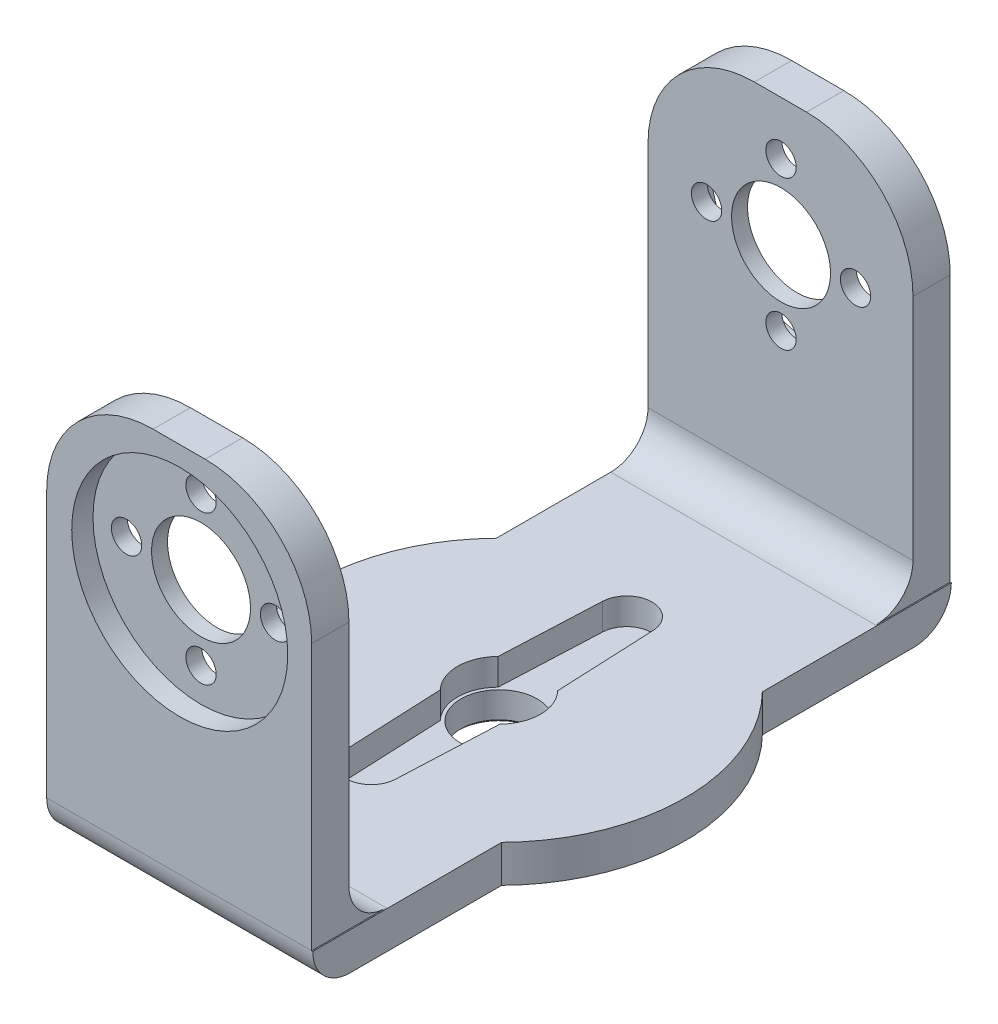
SolidWorks part; units mm, degrees
ref_plane "Alzado" through (0, 0, 0) normal (0, 0, 1) x (1, 0, 0)
ref_plane "Planta" through (0, 0, 0) normal (0, 1, 0) x (1, 0, 0)
ref_plane "Vista lateral" through (0, 0, 0) normal (1, 0, 0) x (0, 0, -1)
ref_plane "Plano1" through (0, 0, 30) normal (0, 0, 1) x (1, 0, 0)
sketch "Croquis1" plane through (0, 0, 0) normal (0, 1, 0) x (1, 0, 0)
  line L0 (1.9972, 12.1065) -> (2.53, 2.1187) construction
  line L1 (-1.9972, 12.1065) -> (-2.53, 2.1187) construction
  line L2 (-1.9972, -12.1065) -> (-2.53, -2.1187) construction
  line L3 (1.9972, -12.1065) -> (2.53, -2.1187) construction
  line L4 (1.9972, 12.1065) -> (2.53, 2.1187)
  line L5 (-1.9972, 12.1065) -> (-2.53, 2.1187)
  line L6 (-1.9972, -12.1065) -> (-2.53, -2.1187)
  line L7 (1.9972, -12.1065) -> (2.53, -2.1187)
  circle A0 centre (0, 0) radius 17.5
  circle A1 centre (0, 0) radius 1.65
  arc A2 (2.53, -2.1187) -> (2.53, 2.1187) centre (0, 0) ccw construction
  arc A3 (1.9972, 12.1065) -> (-1.9972, 12.1065) centre (0, 12) ccw construction
  arc A4 (-2.53, 2.1187) -> (-2.53, -2.1187) centre (0, 0) ccw construction
  arc A5 (-1.9972, -12.1065) -> (1.9972, -12.1065) centre (0, -12) ccw construction
  arc A6 (2.53, -2.1187) -> (2.53, 2.1187) centre (0, 0) ccw
  arc A7 (1.9972, 12.1065) -> (-1.9972, 12.1065) centre (0, 12) ccw
  arc A8 (-2.53, 2.1187) -> (-2.53, -2.1187) centre (0, 0) ccw
  arc A9 (-1.9972, -12.1065) -> (1.9972, -12.1065) centre (0, -12) ccw
  dimension "D1" = 35
  dimension "D2" = 3.3
extrude "Saliente-Extruir1" add sketch "Croquis1" along normal blind 3.5 contours A0 A1 | L6 A9 L7 A6 L4 A7 L5 A8 A1 region at (1.9763, 0, -7.0973) region at (-17.005, 0, 0)
sketch "Croquis2" plane through (0, 3.5, 0) normal (0, 1, 0) x (1, 0, 0)
  line L0 (-1.9972, -12.1065) -> (-2.53, -2.1187) construction
  line L1 (1.9972, -12.1065) -> (2.53, -2.1187) construction
  line L2 (1.9972, 12.1065) -> (2.53, 2.1187) construction
  line L3 (-1.9972, 12.1065) -> (-2.53, 2.1187) construction
  line L4 (-1.9972, -12.1065) -> (-2.53, -2.1187)
  line L5 (1.9972, -12.1065) -> (2.53, -2.1187)
  line L6 (1.9972, 12.1065) -> (2.53, 2.1187)
  line L7 (-1.9972, 12.1065) -> (-2.53, 2.1187)
  arc A1 (-2.53, 2.1187) -> (-2.53, -2.1187) centre (0, 0) ccw construction
  arc A2 (-1.9972, -12.1065) -> (1.9972, -12.1065) centre (0, -12) ccw construction
  arc A3 (2.53, -2.1187) -> (2.53, 2.1187) centre (0, 0) ccw construction
  arc A4 (1.9972, 12.1065) -> (-1.9972, 12.1065) centre (0, 12) ccw construction
  arc A5 (-2.53, 2.1187) -> (-2.53, -2.1187) centre (0, 0) ccw
  arc A6 (-1.9972, -12.1065) -> (1.9972, -12.1065) centre (0, -12) ccw
  arc A7 (2.53, -2.1187) -> (2.53, 2.1187) centre (0, 0) ccw
  arc A8 (1.9972, 12.1065) -> (-1.9972, 12.1065) centre (0, 12) ccw
extrude "Cortar-Extruir1" cut sketch "Croquis2" against normal blind 2.5
sketch "Croquis4" plane through (0, 1, 0) normal (0, 1, 0) x (1, 0, 0)
  circle A1 centre (0, 0) radius 3.3 construction
  circle A2 centre (0, 0) radius 3.3 construction
  circle A3 centre (0, 0) radius 3.6
  dimension "D1" = 0.3
extrude "Cortar-Extruir2" cut sketch "Croquis4" against normal through all both and the other way through all
sketch "Croquis8" plane through (0, 3.5, 0) normal (0, 1, 0) x (1, 0, 0)
  line L0 (3.9, 0) -> (3.9493, 0) construction
  line L1 (1.9972, -12.1065) -> (2.5051, -2.5854) construction
  line L2 (-2.5051, -2.5854) -> (-1.9972, -12.1065) construction
  line L3 (1.9972, -12.1065) -> (2.5051, -2.5854) construction
  line L4 (-2.5051, -2.5854) -> (-1.9972, -12.1065) construction
  line L5 (-2.7955, -2.7194) -> (-2.3743, -12.1065)
  line L6 (2.3743, -12.1065) -> (2.7955, -2.7194)
  line L7 (-3.9, 0) -> (-3.9493, 0) construction
  line L8 (2.3743, -12.1065) -> (1.9972, -12.1065) construction
  line L9 (-1.9972, -12.1065) -> (-2.3743, -12.1065) construction
  line L10 (2.4826, -3.0078) -> (2.7826, -3.0078) construction
  line L11 (-2.4826, -3.0078) -> (-2.7826, -3.0078) construction
  line L12 (2.7955, -2.7194) -> (-2.7955, -2.7194) construction
  line L13 (2.3743, 12.1065) -> (2.7955, 2.7194)
  line L14 (-2.7955, 2.7194) -> (-2.3743, 12.1065)
  line L15 (0, 0) -> (-3.6, 0) construction
  line L16 (0, 0) -> (3.6, 0) construction
  line L17 (-3.6, 0) -> (-3.9, 0) construction
  line L18 (3.6, 0) -> (3.9, 0) construction
  arc A0 (-2.7955, 2.7194) -> (-2.7955, -2.7194) centre (0, 0) ccw
  arc A1 (-1.9972, -12.1065) -> (1.9972, -12.1065) centre (0, -12) ccw construction
  arc A2 (-1.9972, -12.1065) -> (1.9972, -12.1065) centre (0, -12) ccw construction
  arc A3 (-2.3743, -12.1065) -> (2.3743, -12.1065) centre (0, -12) ccw
  arc A4 (-2.7955, -2.7194) -> (-2.4826, -3.0078) centre (0, 0) ccw construction
  arc A5 (2.7955, -2.7194) -> (2.7955, 2.7194) centre (0, 0) ccw
  arc A6 (-2.4826, -3.0078) -> (2.4826, -3.0078) centre (0, 0) ccw construction
  arc A7 (2.4826, -3.0078) -> (2.7955, -2.7194) centre (0, 0) ccw construction
  arc A8 (-2.3743, 12.1065) -> (2.3743, 12.1065) centre (0, 12) cw
  arc A9 (2.5051, -2.5854) -> (2.5051, 2.5854) centre (0, 0) ccw construction
  arc A10 (2.5051, -2.5854) -> (2.5051, 2.5854) centre (0, 0) ccw construction
  arc A11 (-2.5051, 2.5854) -> (-2.5051, -2.5854) centre (0, 0) ccw construction
  arc A12 (-2.5051, 2.5854) -> (-2.5051, -2.5854) centre (0, 0) ccw construction
  dimension "D1" = 0.3
sketch "Croquis5" plane through (0, 0, 0) normal (0, -1, 0) x (1, 0, 0)
  circle A0 centre (0, 0) radius 5.6
  circle A1 centre (0, 0) radius 3.6 construction
  circle A2 centre (0, 0) radius 3.6
  dimension "D1" = 2
extrude "Saliente-Extruir2" add sketch "Croquis5" along normal offset from surface (1.7 mm away) 2.7 up to face at (0, 1, -8.073)
sketch "Croquis6" plane through (0, 0, 30) normal (0, 0, 1) x (1, 0, 0)
  line L0 (17.5, 3.5) -> (-17.5, 3.5) construction
  line L1 (-12.5, 3.5) -> (12.5, 3.5)
  line L2 (-12.5, 3.5) -> (-12.5, 0)
  line L3 (-12.5, 0) -> (12.5, 0)
  line L4 (12.5, 3.5) -> (12.5, 0)
  line L5 (-17.5, 0) -> (17.5, 0) construction
  line L6 (12.5, 0) -> (-12.5, 3.5) construction
  line L7 (-12.5, 0) -> (12.5, 3.5) construction
  line L8 (0, 3.5) -> (0, 1.75) construction
  dimension "D1" = 25
extrude "Saliente-Extruir3" add sketch "Croquis6" against normal up to surface (17.7526 mm away) up to face at (0, 3.5, 17.5)
sketch "Croquis7" plane through (0, 3.5, 0) normal (0, 1, 0) x (1, 0, 0)
  line L0 (-19.25, -30) -> (19.25, -30) construction
  line L1 (12.3996, -30) -> (-12.5, -30)
  line L2 (12.3996, -30) -> (12.3996, -26.5)
  line L3 (12.3996, -26.5) -> (-12.5, -26.5)
  line L4 (-12.5, -30) -> (-12.5, -26.5)
  line L5 (-12.5, -12.2474) -> (-12.5, -30) construction
  dimension "D1" = 3.5
extrude "Saliente-Extruir4" add sketch "Croquis7" along normal blind 35
fillet "Redondeo1" radius 3.5 2 edges at (-0.0502, 3.5, 26.5) (0, 0, 30)
mirror "Simetría1" about plane through (0, 0, 0) normal (0, 0, 1) of "Saliente-Extruir3", "Redondeo1", "Saliente-Extruir4"
ref_plane "Plano2" through (0, 0, 0) normal (0, 0, 1) x (1, 0, 0)
chamfer "Chaflán1" distance 0.254 angle 45 1 edges at (0, -1.7, 3.6)
extrude "Cortar-Extruir3" cut sketch "Croquis8" against normal up to surface (2.5 mm away) up to face at (0, 1, -8.073)
sketch "Croquis10" plane through (0, 0, 30) normal (0, 0, -1) x (-1, 0, 0)
  circle A0 centre (0, 26.5) radius 1
  circle A1 centre (0, 33.5) radius 1.425
  circle A2 centre (7, 26.5) radius 1.425
  circle A3 centre (-7, 26.5) radius 1.425
  circle A4 centre (0, 19.5) radius 1.425
  circle A5 centre (0, 26.5) radius 10.15
  dimension "D1" = 2.85
  dimension "D2" = 2
  dimension "D3" = 20.3
extrude "Cortar-Extruir7" cut sketch "Croquis10" along normal blind 2 contours A5 A3 A1 A0 A2 A4 | A2 | A0 | A1 | A3 | A4 region at (0, 26.5, 30) region at (0, 33.5, 30) region at (-7, 26.5, 30) region at (7, 26.5, 30) region at (0, 19.5, 30) region at (9.8629, 26.5, 30)
sketch "Croquis11" plane through (0, 0, 26.5) normal (0, 0, -1) x (-1, 0, 0)
  line L0 (0, 0) -> (0.0502, 38.5) construction
  line L1 (12.5, 38.5) -> (-12.3996, 38.5) construction
  circle A0 centre (0, 26.5) radius 4.65
  dimension "D1" = 9.3
extrude "Cortar-Extruir8" cut sketch "Croquis11" against normal up to next
sketch "Croquis13" plane through (0, 0, 28) normal (0, 0, 1) x (1, 0, 0)
  circle A0 centre (0, 26.5) radius 10.15 construction
  circle A1 centre (0, 26.5) radius 10.15 construction
  circle A2 centre (0, 19.5) radius 1.425 construction
  circle A3 centre (7, 26.5) radius 1.425 construction
  circle A4 centre (0, 33.5) radius 1.425 construction
  circle A5 centre (-7, 26.5) radius 1.425 construction
  circle A6 centre (0, 19.5) radius 1.425
  circle A7 centre (7, 26.5) radius 1.425
  circle A8 centre (0, 33.5) radius 1.425
  circle A9 centre (-7, 26.5) radius 1.425
extrude "Cortar-Extruir9" cut sketch "Croquis13" against normal up to next
mirror "Simetría2" about plane through (0, 0, 0) normal (0, 0, 1) of "Cortar-Extruir9", "Cortar-Extruir8", "Cortar-Extruir7"
fillet "Redondeo2" radius 10 4 edges at (12.3996, 38.5, 28.25) (-12.5, 38.5, 28.25) (12.3996, 38.5, -28.25) (-12.5, 38.5, -28.25)
equation "\"3.5.00mm\"=10"
